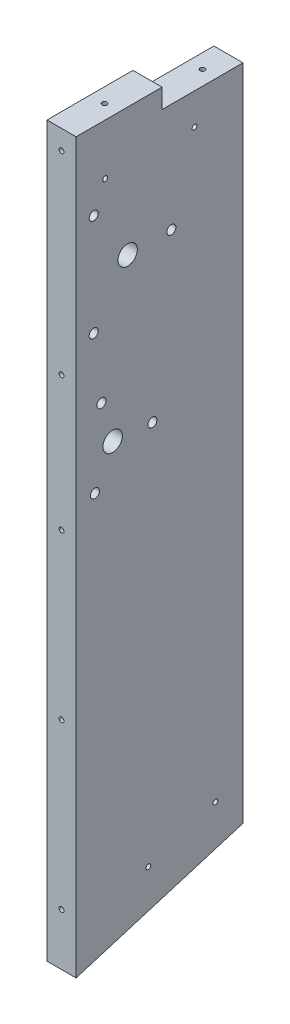
SolidWorks part; units mm, degrees
material "Beech"
ref_plane "Front Plane" through (0, 0, 0) normal (0, 0, 1) x (1, 0, 0)
ref_plane "Top Plane" through (0, 0, 0) normal (0, 1, 0) x (1, 0, 0)
ref_plane "Right Plane" through (0, 0, 0) normal (1, 0, 0) x (0, 0, -1)
sketch "Sketch1" plane through (0, 0, 0) normal (0, 0, 1) x (1, 0, 0)
  line L0 (-331.7795, -427.3421) -> (-331.7795, 0) construction
  line L1 (93.2955, -427.3421) -> (-341.3045, -427.3421) construction
  line L3 (-322.2545, -427.3421) -> (-322.2545, 0)
  line L4 (-341.3045, -427.3421) -> (-341.3045, 0)
  line L5 (-322.2545, -427.3421) -> (-341.3045, -427.3421)
  line L6 (-322.2545, 0) -> (-341.3045, 0)
  line L7 (-341.3045, -427.3421) -> (-341.3045, 12.7) construction
  line L8 (-331.7795, -427.3421) -> (-331.7795, 0) construction
  dimension "D1" = 19.05
extrude "Boss-Extrude1" add sketch "Sketch1" along normal up to surface (53 mm away)
sketch "Sketch2" plane through (0, 0, 53) normal (0, 0, 1) x (1, 0, 0)
  line L0 (-231.3045, 12.7) -> (-341.3045, 12.7) construction
  line L1 (-322.2545, 12.7) -> (-341.3045, 12.7)
  line L4 (-341.3045, 0) -> (-341.3045, -427.3421)
  line L5 (-341.3045, -427.3421) -> (-322.2545, -427.3421)
  line L6 (-322.2545, -427.3421) -> (-322.2545, 0)
  line L7 (-322.2545, 0) -> (-341.3045, 0)
  line L8 (-341.3045, 12.7) -> (-341.3045, -427.3421)
  line L9 (-341.3045, -427.3421) -> (-322.2545, -427.3421)
  line L10 (-322.2545, -427.3421) -> (-322.2545, 12.7)
  dimension "D1" = 0
extrude "Boss-Extrude2" add sketch "Sketch2" along normal up to surface (56.3 mm away)
sketch "Sketch3" plane through (-341.3045, 0, 0) normal (-1, 0, 0) x (0, 0, 1)
  line L0 (0, -427.3421) -> (109.3, -427.3421)
  line L1 (109.3, -427.3421) -> (109.3, -464.2661)
  line L2 (109.3, -464.2661) -> (0, -431.1858)
  line L3 (-12.7, -427.3421) -> (522.1409, -589.2145) construction
  line L4 (0, -431.1858) -> (0, -427.3421)
extrude "Boss-Extrude3" add sketch "Sketch3" against normal through all
hole_wizard "15/64 (0.23438) Diameter Hole1" positions "Sketch5" profile "Sketch6" hole size "15/64" standard "ANSI Inch" end condition through all
sketch "Sketch5" plane through (-341.3045, 0, 0) normal (-1, 0, 0) x (0, 0, 1)
  point P0 (97.7483, -37.836)
  point P3 (97.7483, -104.511)
  point P6 (46.9483, -71.1735)
  point P9 (92.6826, -146.5881)
  point P12 (96.9737, -195.6358)
  point P15 (59.3512, -174.2158)
sketch "Sketch6" plane through (-341.3045, -37.836, 97.7483) normal (0, 1, 0) x (0, 0, 1)
  line L0 (0, 0) -> (0, 19.05)
  line L1 (0, 19.05) -> (2.9766, 19.05)
  line L2 (2.9766, 19.05) -> (2.9766, 0)
  line L5 (2.9766, 0) -> (0, 0)
  line L11 (0, -6.35) -> (0, 107.95) construction
  dimension "Thru Hole Dia." = 5.9533
  dimension "Thru Hole Depth" = 19.05
sketch "Sketch4" plane through (-341.3045, 0, 0) normal (-1, 0, 0) x (0, 0, 1)
  circle A0 centre (75.5233, -71.1735) radius 6.35 construction
  circle A1 centre (75.5233, -71.1735) radius 6.35
  circle A2 centre (85.3394, -171.9421) radius 6.35 construction
  circle A3 centre (85.3394, -171.9421) radius 6.35
extrude "Cut-Extrude1" cut sketch "Sketch4" against normal through all
hole_wizard "Hole1" positions "Sketch7" profile "Sketch8" legacy
sketch "Sketch7" plane through (-124.0045, 10.4243, 122) normal (0, 0, 1) x (-1, 0, 0)
  line L1 (0, 465.9538) -> (0, 167.7243) construction
  point P1 (113.65, 128.8076)
  point P3 (113.65, 23.941)
  point P5 (-94.6, 161.3743)
  point P7 (94.6, 161.3743)
  point P9 (0, 161.3743)
  point P11 (0, 193.1243)
  point P13 (0, 440.5538)
  point P15 (0, 301.9704)
  point P17 (40.9792, 301.9704)
  point P19 (166.7958, 301.9704)
  point P21 (207.775, 440.5538)
  point P23 (207.775, 333.0214)
  point P25 (207.775, 225.489)
  point P27 (207.775, 137.4243)
  point P29 (207.775, 10.4243)
  point P33 (-207.775, 10.4243)
  point P34 (-207.775, 137.4243)
  point P35 (-207.775, 225.489)
  point P36 (-207.775, 333.0214)
  point P37 (-207.775, 440.5538)
  point P38 (-166.7958, 301.9704)
  point P39 (-40.9792, 301.9704)
  point P40 (-113.65, 23.941)
  point P41 (-113.65, 128.8076)
sketch "Sketch8" plane through (-237.6545, -118.3833, 122) normal (1, 0, 0) x (0, -1, 0)
  line L0 (0, 0) -> (0, 32.7039)
  line L1 (0, 32.7039) -> (1.5875, 31.75)
  line L2 (1.5875, 31.75) -> (1.5875, 4.0177)
  line L3 (1.5875, 4.0177) -> (5.08, 0)
  line L4 (5.08, 0) -> (0, 0)
  line L5 (0, -14.3089) -> (0, 102.4216) construction
  line L6 (0, 32.7039) -> (-1.5875, 31.75) construction
  line L7 (-1.5875, 4.0177) -> (-5.08, 0) construction
  dimension "Diameter" = 3.175
  dimension "Depth" = 31.75
  dimension "C-Sink Diameter" = 10.16
  dimension "C-Sink Angle" = 82
  dimension "Drill Angle" = 118
hole_wizard "Hole" positions "Sketch9" profile "Sketch10" legacy
sketch "Sketch9" plane through (-124.0045, 25.4, -155.2867) normal (0, 1, 0) x (-1, 0, 0)
  point P0 (113.65, 236.4367)
  point P2 (207.775, 236.4367)
sketch "Sketch10" plane through (-237.6545, 25.4, 81.15) normal (1, 0, 0) x (0, 0, 1)
  line L0 (0, 0) -> (0, 32.7039)
  line L1 (0, 32.7039) -> (1.5875, 31.75)
  line L2 (1.5875, 31.75) -> (1.5875, 4.0177)
  line L3 (1.5875, 4.0177) -> (5.08, 0)
  line L4 (5.08, 0) -> (0, 0)
  line L5 (0, -14.3089) -> (0, 102.4216) construction
  line L6 (0, 32.7039) -> (-1.5875, 31.75) construction
  line L7 (-1.5875, 4.0177) -> (-5.08, 0) construction
  dimension "Diameter" = 3.175
  dimension "Depth" = 31.75
  dimension "C-Sink Diameter" = 10.16
  dimension "C-Sink Angle" = 82
  dimension "Drill Angle" = 118
hole_wizard "Hole3" positions "Sketch12" profile "Sketch13" legacy
sketch "Sketch12" plane through (-124.0045, 12.7, -155.2867) normal (0, 1, 0) x (-1, 0, 0)
  line L0 (120, 172.2617) -> (217.3, 172.2617) construction
  point P8 (126.35, 172.2617)
  point P10 (207.775, 172.2617)
sketch "Sketch13" plane through (-331.7795, 12.7, 16.975) normal (1, 0, 0) x (0, 0, 1)
  line L0 (0, 0) -> (0, 32.7039)
  line L1 (0, 32.7039) -> (1.5875, 31.75)
  line L2 (1.5875, 31.75) -> (1.5875, 4.0177)
  line L3 (1.5875, 4.0177) -> (5.08, 0)
  line L4 (5.08, 0) -> (0, 0)
  line L5 (0, -14.3089) -> (0, 102.4216) construction
  line L6 (0, 32.7039) -> (-1.5875, 31.75) construction
  line L7 (-1.5875, 4.0177) -> (-5.08, 0) construction
  dimension "Diameter" = 3.175
  dimension "Depth" = 31.75
  dimension "C-Sink Diameter" = 10.16
  dimension "C-Sink Angle" = 82
  dimension "Drill Angle" = 118
hole_wizard "Hole4" positions "Sketch14" profile "Sketch15" legacy
sketch "Sketch14" plane through (-124.0045, 10.4243, -12.7) normal (0, 0, -1) x (1, 0, 0)
  line L12 (0, 0) -> (0, 155.0243) construction
  point P0 (-207.775, 333.0214)
  point P3 (-207.775, 225.489)
  point P6 (-207.775, 137.4243)
  point P9 (-172.1667, 4.0743)
  point P12 (-146.0833, 4.0743)
  point P15 (-94.6, 161.3743)
  point P18 (0, 161.3743)
  point P21 (94.6, 161.3743)
  point P24 (146.0833, 4.0743)
  point P27 (172.1667, 4.0743)
  point P30 (207.775, 137.4243)
  point P33 (207.775, 225.489)
  point P36 (207.775, 333.0214)
  point P39 (166.7958, 301.9704)
  point P42 (40.9792, 301.9704)
  point P45 (-40.9792, 301.9704)
  point P48 (-166.7958, 301.9704)
  point P51 (0, 193.1243)
  point P54 (0, 301.9704)
  point P57 (0, 412.3664)
  point P80 (-126.35, 106.8243)
  point P82 (-126.35, 58.6243)
  point P96 (126.35, 58.6243)
  point P97 (126.35, 106.8243)
sketch "Sketch15" plane through (-331.7795, -322.5971, -12.7) normal (1, 0, 0) x (0, 1, 0)
  line L0 (0, 0) -> (0, 32.7039)
  line L1 (0, 32.7039) -> (1.5875, 31.75)
  line L2 (1.5875, 31.75) -> (1.5875, 4.0177)
  line L3 (1.5875, 4.0177) -> (5.08, 0)
  line L4 (5.08, 0) -> (0, 0)
  line L5 (0, -14.3089) -> (0, 102.4216) construction
  line L6 (0, 32.7039) -> (-1.5875, 31.75) construction
  line L7 (-1.5875, 4.0177) -> (-5.08, 0) construction
  dimension "Diameter" = 3.175
  dimension "Depth" = 31.75
  dimension "C-Sink Diameter" = 10.16
  dimension "C-Sink Angle" = 82
  dimension "Drill Angle" = 118
hole_wizard "Hole5" positions "Sketch16" profile "Sketch17" legacy
sketch "Sketch16" plane through (-124.0045, -363.2296, -268.3751) normal (0, -0.9571, -0.2897) x (1, 0, 0)
  line L4 (-207.775, 822.0847) -> (-207.775, 404.0189) construction
  line L8 (-207.775, 822.0847) -> (-207.775, 717.5683)
  line L9 (-207.775, 717.5683) -> (-207.775, 613.0518)
  line L10 (-207.775, 613.0518) -> (-207.775, 508.5353)
  line L11 (-207.775, 508.5353) -> (-207.775, 404.0189)
  line L12 (-108.65, 822.0847) -> (-108.65, 404.0189) construction
  line L15 (0, 822.0847) -> (0, 692.6022) construction
  line L18 (-207.775, 390.7499) -> (-207.775, 276.5537) construction
  line L22 (-207.775, 390.7499) -> (-207.775, 362.2009)
  line L23 (-207.775, 362.2009) -> (-207.775, 333.6518)
  line L24 (-207.775, 333.6518) -> (-207.775, 305.1027)
  line L25 (-207.775, 305.1027) -> (-207.775, 276.5537)
  line L26 (0, 390.7499) -> (0, 276.5537) construction
  line L30 (0, 276.5537) -> (0, 305.1027)
  line L31 (0, 305.1027) -> (0, 333.6518)
  line L32 (0, 333.6518) -> (0, 362.2009)
  line L33 (0, 362.2009) -> (0, 390.7499)
  point P24 (-207.775, 613.0518)
  point P31 (-207.775, 456.2771)
  point P33 (-207.775, 769.8265)
  point P52 (-108.65, 456.2771)
  point P54 (-108.65, 613.0518)
  point P56 (-108.65, 769.8265)
  point P76 (-207.775, 362.2009)
  point P80 (-207.775, 305.1027)
  point P99 (0, 305.1027)
  point P104 (0, 362.2009)
  point P113 (207.775, 305.1027)
  point P114 (207.775, 362.2009)
  point P115 (108.65, 769.8265)
  point P116 (108.65, 613.0518)
  point P117 (108.65, 456.2771)
  point P118 (207.775, 769.8265)
  point P119 (207.775, 456.2771)
  point P120 (207.775, 613.0518)
sketch "Sketch17" plane through (83.7705, -540.8176, 318.3915) normal (1, 0, 0) x (0, 0.2897, -0.9571)
  line L0 (0, 0) -> (0, 32.7039)
  line L1 (0, 32.7039) -> (1.5875, 31.75)
  line L2 (1.5875, 31.75) -> (1.5875, 4.0177)
  line L3 (1.5875, 4.0177) -> (5.08, 0)
  line L4 (5.08, 0) -> (0, 0)
  line L5 (0, -14.3089) -> (0, 102.4216) construction
  line L6 (0, 32.7039) -> (-1.5875, 31.75) construction
  line L7 (-1.5875, 4.0177) -> (-5.08, 0) construction
  dimension "Diameter" = 3.175
  dimension "Depth" = 31.75
  dimension "C-Sink Diameter" = 10.16
  dimension "C-Sink Angle" = 82
  dimension "Drill Angle" = 118
hole_wizard "Hole6" positions "Sketch18" profile "Sketch19" legacy
sketch "Sketch18" plane through (-354.0045, 10.4243, -155.2867) normal (-1, 0, 0) x (0, -0.9959, 0.09)
  line L0 (54.6742, 260.7254) -> (44.8416, 151.8686) construction
  line L6 (458.2175, 188.8136) -> (426.7882, 117.3689) construction
  line L11 (443.4217, 288.0956) -> (513.4071, 262.4897) construction
  line L16 (479.186, 443.3317) -> (498.5551, 428.1819) construction
  line L19 (643.2075, 626.7743) -> (602.3132, 525.5573) construction
  line L24 (664.0363, 618.3589) -> (454.7061, 100.2486) construction
  line L28 (664.0363, 618.3589) -> (611.7037, 488.8313)
  line L29 (611.7037, 488.8313) -> (559.3712, 359.3037)
  line L30 (559.3712, 359.3037) -> (507.0387, 229.7761)
  line L31 (507.0387, 229.7761) -> (454.7061, 100.2486)
  point P12 (52.9605, 241.7526)
  point P14 (47.6978, 183.4898)
  point P29 (434.4591, 134.8062)
  point P31 (453.1036, 177.1887)
  point P48 (478.4144, 275.2927)
  point P60 (488.8705, 435.7568)
  point P79 (636.0712, 609.1114)
  point P81 (609.4494, 543.2202)
  point P98 (559.3712, 359.3037)
  point P100 (507.0387, 229.7761)
  point P112 (637.87, 553.5951)
sketch "Sketch19" plane through (-354.0045, -575.0582, 453.4463) normal (0, 1, 0) x (0, 0, 1)
  line L0 (0, 0) -> (0, 32.7039)
  line L1 (0, 32.7039) -> (1.5875, 31.75)
  line L2 (1.5875, 31.75) -> (1.5875, 4.0177)
  line L3 (1.5875, 4.0177) -> (5.08, 0)
  line L4 (5.08, 0) -> (0, 0)
  line L5 (0, -14.3089) -> (0, 102.4216) construction
  line L6 (0, 32.7039) -> (-1.5875, 31.75) construction
  line L7 (-1.5875, 4.0177) -> (-5.08, 0) construction
  dimension "Diameter" = 3.175
  dimension "Depth" = 31.75
  dimension "C-Sink Diameter" = 10.16
  dimension "C-Sink Angle" = 82
  dimension "Drill Angle" = 118
